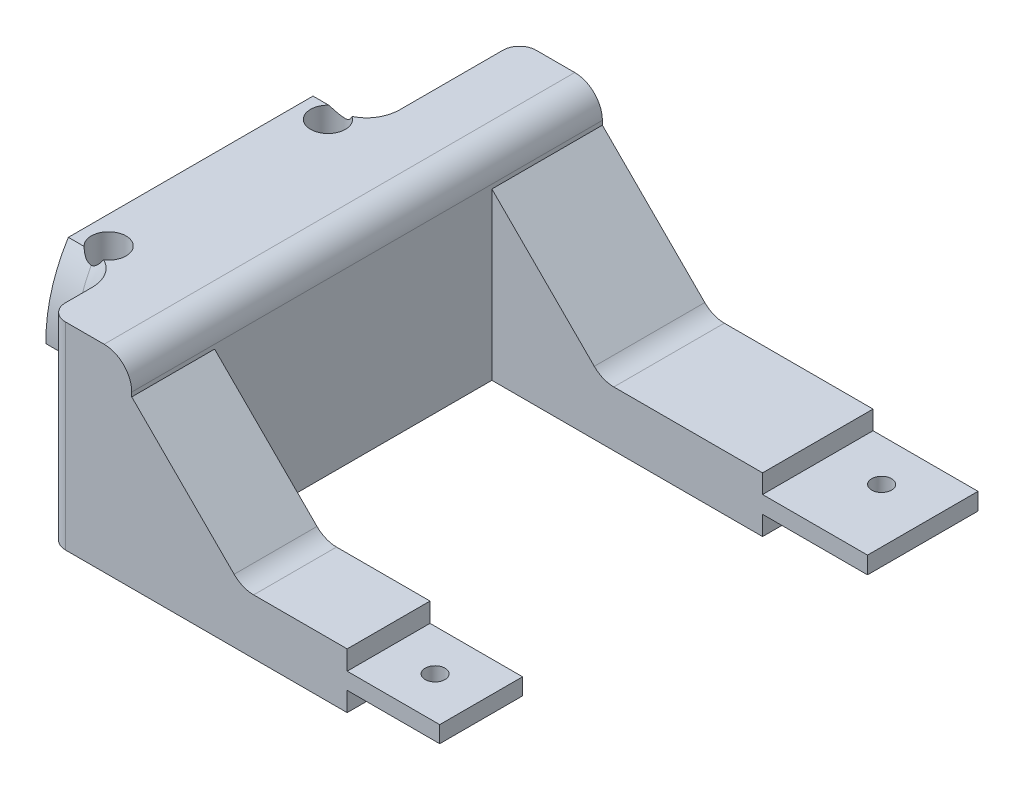
SolidWorks part; units mm, degrees
ref_plane "Plano frontal" through (0, 0, 0) normal (0, 0, 1) x (1, 0, 0)
ref_plane "Plano superior" through (0, 0, 0) normal (0, 1, 0) x (1, 0, 0)
ref_plane "Plano direito" through (0, 0, 0) normal (1, 0, 0) x (0, 0, -1)
sketch "Esboço1" plane through (0, 0, 0) normal (0, 0, 1) x (1, 0, 0)
  line L1 (8.375, -1.5) -> (-8.375, -1.5)
  line L2 (8.375, -1.5) -> (8.375, 1.5)
  line L3 (8.375, 1.5) -> (-8.375, 1.5)
  line L4 (-8.375, -1.5) -> (-8.375, 1.5)
  line L5 (8.375, -1.5) -> (-8.375, 1.5) construction
  line L6 (8.375, 1.5) -> (-8.375, -1.5) construction
  point P0 (0, 0)
  dimension "D1" = 16.75
  dimension "D2" = 3
extrude "Ressalto-extrusão1" add sketch "Esboço1" along normal mid plane 20
sketch "Esboço2" plane through (0, 0, 10) normal (0, 0, 1) x (1, 0, 0)
  line L0 (-8.375, 1.5) -> (-8.375, -1.5) construction
  line L1 (-8.375, 5) -> (-47.375, 5)
  line L2 (-8.375, 5) -> (-8.375, -5)
  line L3 (-8.375, -5) -> (-47.375, -5)
  line L4 (-47.375, 5) -> (-47.375, -5)
  point P6 (-8.375, 0)
  point P7 (-8.375, 0)
  dimension "D1" = 10
  dimension "D2" = 39
extrude "Ressalto-extrusão2" add sketch "Esboço2" against normal through all
sketch "Esboço3" plane through (0, 5, 0) normal (0, 1, 0) x (1, 0, 0)
  line L0 (-8.375, 10) -> (-47.375, 10) construction
  line L1 (-47.375, -10) -> (-62.375, -10)
  line L2 (-47.375, -10) -> (-47.375, 55.2)
  line L3 (-47.375, 75.2) -> (-62.375, 75.2)
  line L4 (-62.375, -10) -> (-62.375, 75.2)
  line L5 (-47.375, 75.2) -> (20.625, 75.2)
  line L6 (-47.375, 75.2) -> (-47.375, 55.2) construction
  line L7 (-47.375, 55.2) -> (20.625, 55.2)
  line L8 (20.625, 75.2) -> (20.625, 55.2)
  line L9 (20.625, 75.2043) -> (20.625, 55.2043) construction
  line M8 (-47.375, 10) -> (-47.375, -10)
  dimension "D2" = 15
  dimension "D3" = 45.2
  dimension "D4" = 20
extrude "Ressalto-extrusão3" add sketch "Esboço3" against normal through all contours L6 L3 L4 L1 L2 M8 | L5 L6 L7 L8 region at (-54.875, 5, -32.6) region at (-13.375, 5, -65.2)
sketch "Esboço4" plane through (0, 0, -75.2) normal (0, 0, -1) x (-1, 0, 0)
  line L1 (-20.625, -5) -> (-1.625, -5)
  line L2 (-20.625, -5) -> (-20.625, -1.5)
  line L3 (-20.625, -1.5) -> (-1.625, -1.5)
  line L4 (-1.625, -5) -> (-1.625, -1.5)
  line L5 (-20.625, 5) -> (-1.625, 5)
  line L6 (-20.625, 5) -> (-20.625, 1.6)
  line L7 (-20.625, 1.6) -> (-1.625, 1.6)
  line L8 (-1.625, 5) -> (-1.625, 1.6)
  dimension "D1" = 3.1
extrude "Corte-extrusão1" cut sketch "Esboço4" against normal up to next
sketch "Esboço5" plane through (-62.375, 0, 0) normal (-1, 0, 0) x (0, 0, 1)
  line L6 (10, -5) -> (10, 5) construction
  line L7 (-75.2, 5) -> (10, 5)
  line L8 (-75.2, 5) -> (-75.2, 30.76)
  line L9 (-75.2, 30.76) -> (10, 30.76)
  line L10 (10, 5) -> (10, 30.76)
  circle A4 centre (-25.67, 16.76) radius 11 construction
  dimension "D1" = 3
extrude "Ressalto-extrusão4" add sketch "Esboço5" against normal up to surface (15 mm away)
sketch "Esboço6" plane through (-62.375, 0, 0) normal (-1, 0, 0) x (0, 0, 1)
  line L0 (-36.67, 16.76) -> (-38.52, 16.76)
  line L1 (-38.52, 16.76) -> (-40.52, 14.76)
  line L2 (-40.52, 14.76) -> (-50.52, 14.76)
  line L3 (-50.52, 14.76) -> (-51.8617, 16.1017)
  line L4 (-50.52, 14.76) -> (-51.8617, 16.1017) construction
  line L5 (-25.67, 16.76) -> (-25.67, 27.76) construction
  line L6 (-0.82, 14.76) -> (0.5217, 16.1017)
  line L7 (-10.82, 14.76) -> (-0.82, 14.76)
  line L8 (-12.82, 16.76) -> (-10.82, 14.76)
  line L9 (-14.67, 16.76) -> (-12.82, 16.76)
  line L10 (-47.8159, 30.76) -> (-3.5241, 30.76)
  line L11 (10, 30.76) -> (-75.2, 30.76) construction
  circle A0 centre (-25.67, 16.76) radius 26.2 construction
  arc A1 (-14.67, 16.76) -> (-36.67, 16.76) centre (-25.67, 16.76) ccw
  arc A2 (0.5217, 16.1017) -> (-3.5241, 30.76) centre (-25.67, 16.76) ccw
  arc A3 (-47.8159, 30.76) -> (-51.8617, 16.1017) centre (-25.67, 16.76) ccw
extrude "Ressalto-extrusão5" add sketch "Esboço6" along normal blind 10
sketch "Esboço7" plane through (0, 14.76, 0) normal (0, -1, 0) x (1, 0, 0)
  circle A0 centre (-67.375, -5.82) radius 1.8
  circle A1 centre (-67.375, -45.52) radius 1.8
  dimension "D1" = 3.6
extrude "Corte-extrusão2" cut sketch "Esboço7" against normal up to next
sketch "Esboço8" plane through (0, 30.76, 0) normal (0, 1, 0) x (1, 0, 0)
  circle A0 centre (-67.375, 45.52) radius 3.15
  circle A1 centre (-67.375, 5.82) radius 3.15
  dimension "D1" = 6.3
extrude "Corte-extrusão3" cut sketch "Esboço8" against normal blind 5
chamfer "Chanfro1" distance 20 angle 45 2 edges at (-47.375, 5, -65.2) (-47.375, 5, 0)
fillet "Filete1" radius 5 2 edges at (-62.375, 23.7308, -50.9256) (-62.375, 23.7308, -0.4144)
fillet "Filete4" radius 3 2 edges at (-62.375, 12.88, 10) (-62.375, 12.88, -75.2)
fillet "Filete5" radius 5 1 edges at (-47.375, 30.76, -32.6)
fillet "Filete6" radius 5 2 edges at (-27.375, 5, -65.2) (-27.375, 5, 0)
sketch "Esboço9" plane through (0, 1.5, 0) normal (0, 1, 0) x (1, 0, 0)
  circle A0 centre (0, -2.46) radius 1.8
  circle A1 centre (10.815, 67.565) radius 1.8
  dimension "D1" = 3.6
  dimension "D2" = 3.6
extrude "Corte-extrusão4" cut sketch "Esboço9" against normal up to next and the other way blind 5
sketch "Esboço10" plane through (0, 30.76, 0) normal (0, 1, 0) x (1, 0, 0)
  line L0 (8.375, -10) -> (8.375, 10) construction
  line L1 (-47.375, 10) -> (8.375, 10)
  line L2 (-47.375, 10) -> (-47.375, 5)
  line L3 (-47.375, 5) -> (8.375, 5)
  line L4 (8.375, 10) -> (8.375, 5)
  line L5 (20.625, 55.2) -> (1.625, 55.2) construction
  dimension "D1" = 50.2
extrude "Corte-extrusão5" cut sketch "Esboço10" against normal through all
